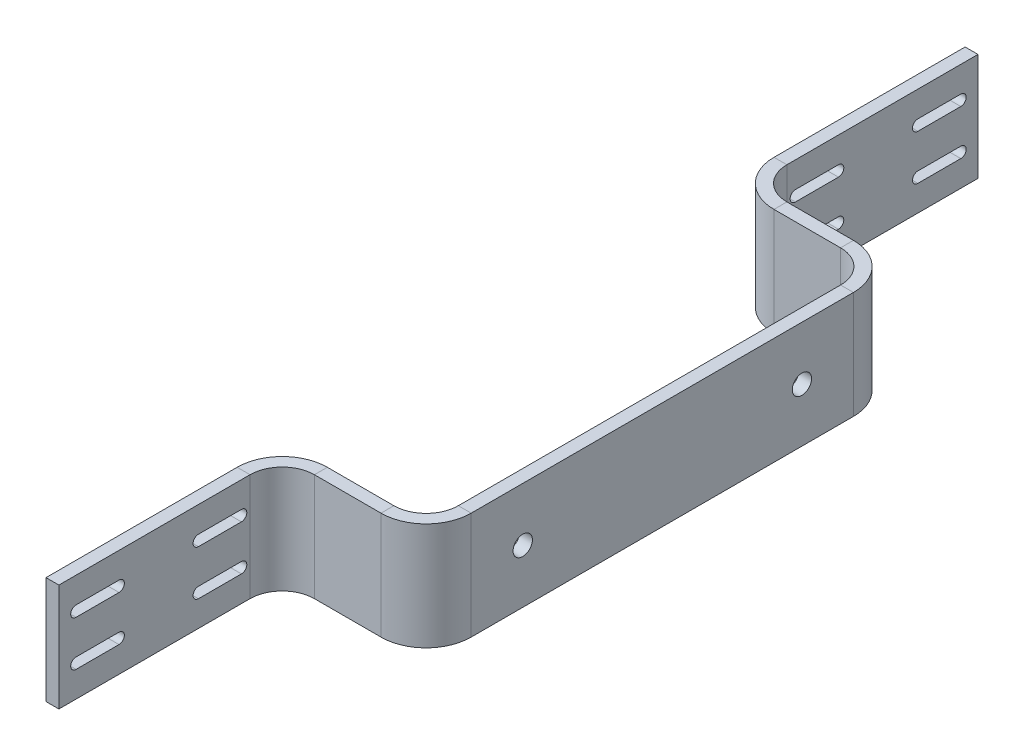
SolidWorks part; units mm, degrees
note: The reader was unsure of these and kept them because the rebuilt part matched: flange length of "Edge-Flange1", "Edge-Flange2".
material "Plain Carbon Steel"
ref_plane "Front Plane" through (0, 0, 0) normal (0, 0, 1) x (1, 0, 0)
ref_plane "Top Plane" through (0, 0, 0) normal (0, 1, 0) x (1, 0, 0)
ref_plane "Right Plane" through (0, 0, 0) normal (1, 0, 0) x (0, 0, -1)
sketch "Sketch1" plane through (0, 0, 0) normal (1, 0, 0) x (0, 0, -1)
  line L1 (-55, -25) -> (55, -25)
  line L2 (-55, -25) -> (-55, 25)
  line L3 (-55, 25) -> (55, 25)
  line L4 (55, -25) -> (55, 25)
  line L5 (-55, -25) -> (55, 25) construction
  line L6 (-55, 25) -> (55, -25) construction
  point P0 (0, 0)
  dimension "D1" = 50
  dimension "D2" = 110
base flange "Base-Flange1" sketch "Sketch1" thickness 6 reverse thickness direction no parameters "D1"=15
sketch "Sketch5" plane through (-6, 0, 0) normal (-1, 0, 0) x (0, 0, 1)
  line L0 (-30, 10.5) -> (-10, 10.5) construction
  line L3 (-30, 13) -> (-10, 13)
  line L4 (-30, 8) -> (-10, 8)
  line L6 (-55, -25) -> (-55, 25) construction
  arc A2 (-30, 13) -> (-30, 8) centre (-30, 10.5) ccw
  arc A3 (-10, 8) -> (-10, 13) centre (-10, 10.5) ccw
  point P2 (-20, 10.5)
  dimension "D1" = 20
  dimension "D2" = 5
  dimension "D3" = 10.5
  dimension "D4" = 25
extrude "Cut-Extrude1" cut sketch "Sketch5" against normal blind 10
pattern_linear "LPattern1" count 2 spacing 57 along (0, 0, 1) of "Cut-Extrude1"
mirror "Mirror1" about plane through (0, 0, 0) normal (0, 1, 0) of "LPattern1", "Cut-Extrude1"
edge flange "Edge-Flange1" sketch "Sketch11" flange angle 90 flange length 73 flange position material inside bend radius 15 thickness 6 relief rectangular parameters "D6"=10
bend "EdgeBend3" bend radius 15 bend angle 90 parameters "D5"=1
sketch "Sketch11" plane through (0, 0, -55) normal (0, 0, -1) x (0, 1, 0)
  line L1 (-25, 0) -> (25, 0) construction
  line L2 (25, 0) -> (25, 67)
  line L3 (25, 67) -> (-25, 67)
  line L4 (-25, 67) -> (-25, 0)
  line L5 (-25, 0) -> (25, 0)
edge flange "Edge-Flange2" sketch "Sketch13" flange angle 90 flange length 110 flange position material inside bend radius 15 thickness 6 relief rectangular parameters "D6"=10
bend "EdgeBend4" bend radius 15 bend angle 90 parameters "D5"=2
sketch "Sketch13" plane through (67, 0, -55) normal (1, 0, 0) x (0, -1, 0)
  line L0 (-25, 0) -> (25, 0) construction
  line L1 (-25, 0) -> (25, 0)
  line L2 (-25, 0) -> (-25, 104)
  line L3 (-25, 104) -> (25, 104)
  line L4 (25, 104) -> (25, 0)
sketch "Sketch9" plane through (61, 0, 0) normal (-1, 0, 0) x (0, 0, 1)
  line L2 (-159, -25) -> (-159, 25) construction
  circle A0 centre (-94, 0) radius 4.5
  dimension "D1" = 9
  dimension "D2" = 65
extrude "Cut-Extrude2" cut sketch "Sketch9" against normal blind 10
ref_plane "Plane1" through (0, 0, -159) normal (0, 0, -1) x (-1, 0, 0)
mirror "Mirror2" about plane through (67, 25, -159) normal (0, 0, 1) of bodies 111
bend "MirrorBend3" bend radius 15 bend angle 90 parameters "D5"=3
bend "MirrorBend4" bend radius 15 bend angle 90 parameters "D5"=4
sketch "Bend-Lines1" [suppressed] plane through (0, 0, 0) normal (0, 1, 0) x (1, 0, 0)
sketch "Bounding-Box1" [suppressed] plane through (0, 0, 0) normal (0, 1, 0) x (1, 0, 0)
sheet metal parameters "Sheet-Metal2" thickness 6 parameters "D1"=15
flat pattern "Flat-Pattern2" [suppressed]
sketch "Bend-Lines2" plane through (0, 0, 0) normal (0, 1, 0) x (1, 0, 0)
sketch3d "Bounding-Box2" [suppressed]
  line L0 (55, -25, 0) -> (-55, -25, 0) construction
  line L1 (55, 25, 0) -> (-55, 25, 0) construction
  line L2 (55, -25, 0) -> (55, 25, 0) construction
  line L3 (-55, -25, 0) -> (-55, 25, 0) construction
sheet metal parameters "Sheet-Metal5" thickness 6 parameters "D1"=15
flat pattern "Flat-Pattern2"
sketch "Bend-Lines2" plane through (0, 0, 0) normal (1, 0, 0) x (0, 0, -1)
  line L2 (48.1372, -25) -> (48.1372, 25) construction
  line L3 (48.1372, -25) -> (48.1372, 25) construction
  point P0 (-48.1372, 25)
  point P1 (-48.1372, -25)
sketch3d "Bounding-Box2" [suppressed]
  line L0 (126.2743, -25, 0) -> (-55, -25, 0) construction
  line L1 (126.2743, 25, 0) -> (-55, 25, 0) construction
  line L2 (126.2743, -25, 0) -> (126.2743, 25, 0) construction
  line L3 (-55, -25, 0) -> (-55, 25, 0) construction
bend of the flat pattern "Flatten-<EdgeBend3>1"
sheet metal parameters "Sheet-Metal7" thickness 6 parameters "D1"=15
flat pattern "Flat-Pattern2"
sketch "Bend-Lines2" plane through (0, 0, 0) normal (1, 0, 0) x (0, 0, -1)
  line L0 (-28.1372, 50) -> (-28.1372, -50) construction
  line L1 (-28.1372, 50) -> (-28.1372, -50) construction
sketch3d "Bounding-Box2" [suppressed]
  line L0 (35, -50, 0) -> (-192.2743, -50, 0) construction
  line L1 (35, 50, 0) -> (-192.2743, 50, 0) construction
  line L2 (35, -50, 0) -> (35, 50, 0) construction
  line L3 (-192.2743, -50, 0) -> (-192.2743, 50, 0) construction
sheet metal parameters "Sheet-Metal8" thickness 6 parameters "D1"=15
flat pattern "Flat-Pattern2"
sketch "Bend-Lines2" plane through (0, 0, 0) normal (1, 0, 0) x (0, 0, -1)
  line L0 (-43.1372, 17.5) -> (-43.1372, -17.5) construction
  line L1 (-43.1372, 17.5) -> (-43.1372, -17.5) construction
sketch3d "Bounding-Box2" [suppressed]
  line L0 (50, -17.5, 0) -> (-207.2743, -17.5, 0) construction
  line L1 (50, 17.5, 0) -> (-207.2743, 17.5, 0) construction
  line L2 (50, -17.5, 0) -> (50, 17.5, 0) construction
  line L3 (-207.2743, -17.5, 0) -> (-207.2743, 17.5, 0) construction
sheet metal parameters "Sheet-Metal10" thickness 6 parameters "D1"=15
flat pattern "Flat-Pattern2" [suppressed]
sketch "Bend-Lines2" plane through (0, 0, 0) normal (1, 0, 0) x (0, 0, -1)
  line L0 (-23.1372, 40) -> (-23.1372, -40) construction
  line L1 (-23.1372, 40) -> (-23.1372, -40) construction
  line L2 (-180.4115, 40) -> (-180.4115, -40) construction
  line L3 (-180.4115, 40) -> (-180.4115, -40) construction
sketch3d "Bounding-Box2" [suppressed]
  line L0 (30, -40, 0) -> (-233.5487, -40, 0) construction
  line L1 (30, 40, 0) -> (-233.5487, 40, 0) construction
  line L2 (30, -40, 0) -> (30, 40, 0) construction
  line L3 (-233.5487, -40, 0) -> (-233.5487, 40, 0) construction
bend of the flat pattern "Flatten-<EdgeBend3>2"
bend of the flat pattern "Flatten-<EdgeBend4>1"
sheet metal parameters "Sheet-Metal11" thickness 6 parameters "D1"=15
flat pattern "Flat-Pattern2"
sketch "Bend-Lines2" plane through (0, 0, 0) normal (1, 0, 0) x (0, 0, -1)
  line L4 (119.4115, -25) -> (119.4115, 25) construction
  line L5 (48.1372, -25) -> (48.1372, 25) construction
  line L6 (119.4115, -25) -> (119.4115, 25) construction
  line L7 (48.1372, -25) -> (48.1372, 25) construction
sketch3d "Bounding-Box2" [suppressed]
  line L0 (337.5487, -25, 0) -> (-55, -25, 0) construction
  line L1 (337.5487, 25, 0) -> (-55, 25, 0) construction
  line L2 (337.5487, -25, 0) -> (337.5487, 25, 0) construction
  line L3 (-55, -25, 0) -> (-55, 25, 0) construction
bend of the flat pattern "Flatten-<EdgeBend3>3"
bend of the flat pattern "Flatten-<EdgeBend4>2"
sheet metal parameters "Sheet-Metal14" thickness 6 parameters "D1"=15
flat pattern "Flat-Pattern2"
sketch "Bend-Lines2" plane through (0, 0, 0) normal (1, 0, 0) x (0, 0, -1)
  line L0 (-48.1372, -25) -> (-48.1372, 25) construction
  line L1 (-48.1372, -25) -> (-48.1372, 25) construction
  line L2 (-119.4115, 25) -> (-119.4115, -25) construction
  line L3 (-119.4115, 25) -> (-119.4115, -25) construction
sketch3d "Bounding-Box2" [suppressed]
  line L0 (55, -25, 0) -> (-337.5487, -25, 0) construction
  line L1 (55, 25, 0) -> (-337.5487, 25, 0) construction
  line L2 (55, -25, 0) -> (55, 25, 0) construction
  line L3 (-337.5487, -25, 0) -> (-337.5487, 25, 0) construction
sheet metal parameters "Sheet-Metal15" thickness 6 parameters "D1"=15
flat pattern "Flat-Pattern15"
sketch "Bend-Lines3" plane through (0, 0, 0) normal (1, 0, 0) x (0, 0, -1)
  line L8 (313.6858, -25) -> (313.6858, 25) construction
  line L9 (372.9602, -25) -> (372.9602, 25) construction
  line L10 (107.4115, -25) -> (107.4115, 25) construction
  line L11 (48.1372, -25) -> (48.1372, 25) construction
  line L12 (313.6858, -25) -> (313.6858, 25) construction
  line L13 (372.9602, -25) -> (372.9602, 25) construction
  line L14 (107.4115, -25) -> (107.4115, 25) construction
  line L15 (48.1372, -25) -> (48.1372, 25) construction
sketch3d "Bounding-Box3" [suppressed]
  line L0 (476.0973, -25, 0) -> (-55, -25, 0) construction
  line L1 (476.0973, 25, 0) -> (-55, 25, 0) construction
  line L2 (476.0973, -25, 0) -> (476.0973, 25, 0) construction
  line L3 (-55, -25, 0) -> (-55, 25, 0) construction
bend of the flat pattern "Flatten-<EdgeBend4>3"
bend of the flat pattern "Flatten-<EdgeBend3>4"
bend of the flat pattern "Flatten-<MirrorBend3>1"
bend of the flat pattern "Flatten-<MirrorBend4>1"
